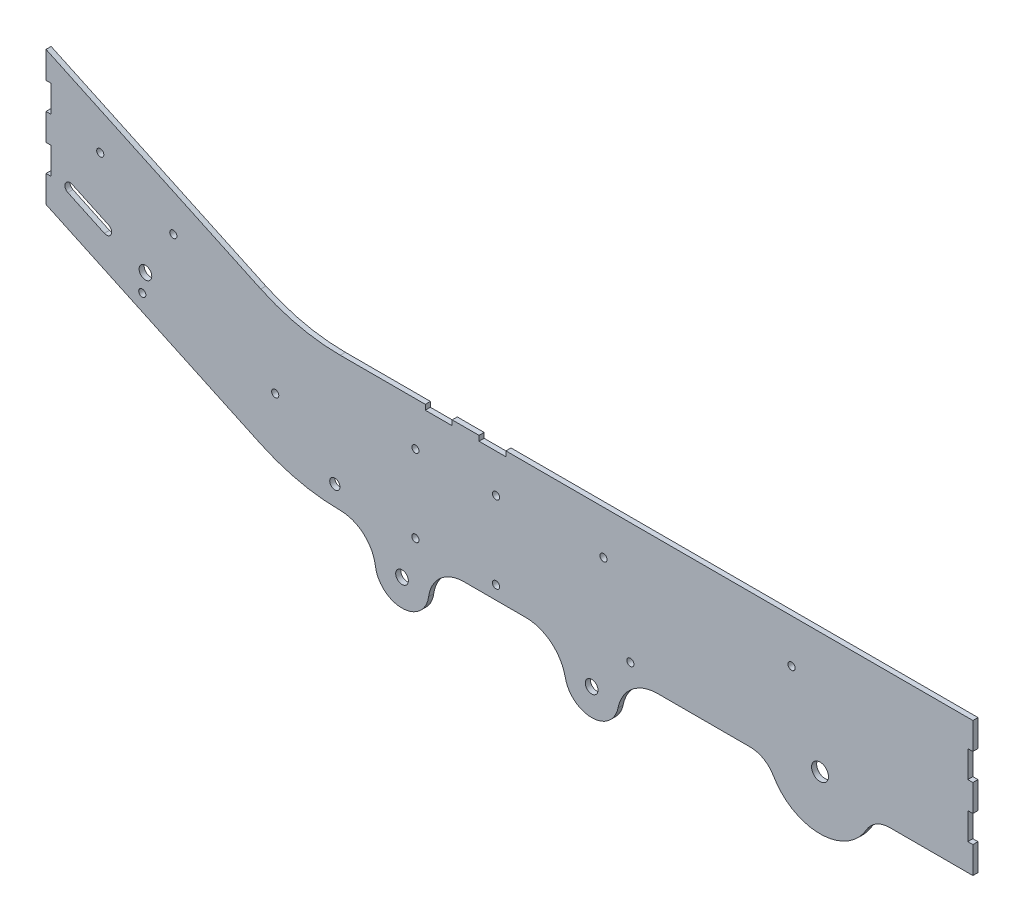
SolidWorks part; units mm, degrees
material "1060 Alloy"
ref_plane "Front Plane" through (0, 0, 0) normal (0, 0, 1) x (1, 0, 0)
ref_plane "Top Plane" through (0, 0, 0) normal (0, 1, 0) x (1, 0, 0)
ref_plane "Right Plane" through (0, 0, 0) normal (1, 0, 0) x (0, 0, -1)
sketch "standoff holes lower" plane through (0, 0, 0) normal (0, 0, 1) x (1, 0, 0)
  circle A7 centre (95.25, 85.725) radius 3.3782
  circle A8 centre (95.25, 12.7) radius 3.3782
  circle A9 centre (171.45, 12.7) radius 3.3782
  circle A10 centre (171.45, 85.725) radius 3.3782
  circle A12 centre (298.45, 12.7) radius 3.3782
  circle A13 centre (450.85, 85.725) radius 3.3782
  circle A16 centre (273.05, 85.725) radius 3.3782
  point P21 (0, 0)
sketch "axle holes lower" plane through (0, 0, 0) normal (0, 0, 1) x (1, 0, 0)
  line L10 (514.35, 98.425) -> (75.4368, 98.425) construction
  line L11 (66.0749, 94.3067) -> (3.3381, 25.8666) construction
  line L12 (0, 17.2849) -> (0, 12.7) construction
  line L13 (12.7, 0) -> (514.35, 0) construction
  line L14 (527.05, 12.7) -> (527.05, 85.725) construction
  circle A1 centre (247.65, 15.24) radius 4.826
  circle A4 centre (19.05, 19.05) radius 4.826
  arc A10 (527.05, 85.725) -> (514.35, 98.425) centre (514.35, 85.725) ccw construction
  arc A11 (75.4368, 98.425) -> (66.0749, 94.3067) centre (75.4368, 85.725) ccw construction
  arc A12 (3.3381, 25.8666) -> (0, 17.2849) centre (12.7, 17.2849) ccw construction
  arc A13 (0, 12.7) -> (12.7, 0) centre (12.7, 12.7) ccw construction
  arc A14 (514.35, 0) -> (527.05, 12.7) centre (514.35, 12.7) ccw construction
  circle A15 centre (476.25, 19.05) radius 4.826
sketch "lower box" plane through (0, 0, 0) normal (0, 0, 1) x (1, 0, 0)
  line L1 (622.3, 0) -> (-254, 0) construction
  line L2 (622.3, 0) -> (622.3, 25.4) construction
  line L3 (622.3, 127) -> (-254, 127) construction
  line L4 (-254, 0) -> (-254, 127) construction
  line L6 (527.05, 12.7) -> (527.05, 85.725) construction
  line L7 (622.3, 101.6) -> (622.3, 127) construction
  line L8 (622.3, 101.6) -> (617.474, 101.6) construction
  line L10 (622.3, 76.2) -> (617.474, 76.2) construction
  line L11 (617.474, 101.6) -> (617.474, 76.2) construction
  line L12 (622.3, 50.8) -> (617.474, 50.8) construction
  line L14 (622.3, 25.4) -> (617.474, 25.4) construction
  line L15 (617.474, 50.8) -> (617.474, 25.4) construction
  line L16 (622.3, 50.8) -> (622.3, 76.2) construction
  dimension "D1" = 127
  dimension "D2" = 876.3
  dimension "D3" = 95.25
  dimension "D4" = 4.826
sketch "alxe holes upper" plane through (0, 0, 0) normal (0, 0, 1) x (1, 0, 0)
  line L0 (-219.7848, 130.4205) -> (-230.5193, 107.4003) construction
  line L1 (-230.5193, 107.4003) -> (8.3155, -3.9702) construction
  line L3 (8.3155, -3.9702) -> (19.05, 19.05) construction
  line L4 (622.3, 0) -> (-254, 0) construction
  circle A0 centre (19.05, 19.05) radius 4.826 construction
  circle A2 centre (-219.7848, 130.4205) radius 4.826
  circle A3 centre (19.05, 19.05) radius 4.826
  dimension "D4" = 25
  dimension "D1" = 25.4
  dimension "D2" = 25.4
  dimension "D3" = 263.525
sketch "standoff holes upper" plane through (0, 0, 0) normal (0, 0, 1) x (1, 0, 0)
  line L0 (-162.9561, 84.3028) -> (-166.1764, 77.3967) construction
  line L1 (-226.6865, 105.613) -> (11.2395, -5.3337) construction
  line L4 (-37.2808, 64.9356) -> (-55.5295, 25.8012) construction
  line L5 (-230.5193, 107.4003) -> (8.3155, -3.9702) construction
  circle A2 centre (-162.9561, 84.3028) radius 3.3782
  circle A3 centre (-37.2808, 64.9356) radius 3.3782
  dimension "D2" = 7.62
  dimension "D1" = 43.18
sketch "upper shadow" plane through (0, 0, 0) normal (0, 0, 1) x (1, 0, 0)
  line L0 (-230.5193, 107.4003) -> (8.3155, -3.9702) construction
  line L4 (33.2535, 40.1076) -> (-204.2179, 150.8423) construction
  line L5 (-230.5193, 107.4003) -> (8.3155, -3.9702) construction
  arc A4 (8.3155, -3.9702) -> (33.2535, 40.1076) centre (19.05, 19.05) ccw construction
  arc A5 (-204.2179, 150.8423) -> (-230.5193, 107.4003) centre (-216.8161, 128.7868) ccw construction
  dimension "D1" = 25.4
  dimension "D2" = 25.4
sketch "upper box" plane through (0, 0, 0) normal (0, 0, 1) x (1, 0, 0)
  line L0 (-15.224, 0) -> (-254, 111.3431) construction
  line L1 (622.3, 0) -> (-254, 0) construction
  line L2 (-254, 111.3431) -> (-254, 136.7431) construction
  line L3 (-254, 238.3431) -> (257.1283, 0) construction
  line L4 (12.7, 0) -> (514.35, 0) construction
  line L5 (-254, 0) -> (-254, 127) construction
  line L6 (-230.5193, 107.4003) -> (8.3155, -3.9702) construction
  line L7 (-254, 212.9431) -> (-254, 238.3431) construction
  line L8 (-254, 212.9431) -> (-249.174, 212.9431) construction
  line L9 (-254, 162.1431) -> (-254, 187.5431) construction
  line L10 (-254, 187.5431) -> (-249.174, 187.5431) construction
  line L11 (-249.174, 212.9431) -> (-249.174, 187.5431) construction
  line L12 (-254, 162.1431) -> (-249.174, 162.1431) construction
  line L14 (-254, 136.7431) -> (-249.174, 136.7431) construction
  line L15 (-249.174, 162.1431) -> (-249.174, 136.7431) construction
  dimension "D1" = 127
  dimension "D2" = 6.35
  dimension "D3" = 4.826
sketch "outer face" plane through (0, 0, 0) normal (0, 0, 1) x (1, 0, 0)
  line L0 (622.3, 0) -> (-254, 0) construction
  line L1 (622.3, 0) -> (622.3, 25.4) construction
  line L2 (622.3, 25.4) -> (617.474, 25.4) construction
  line L3 (617.474, 50.8) -> (617.474, 25.4) construction
  line L4 (622.3, 50.8) -> (617.474, 50.8) construction
  line L5 (622.3, 50.8) -> (622.3, 76.2) construction
  line L6 (622.3, 76.2) -> (617.474, 76.2) construction
  line L7 (617.474, 101.6) -> (617.474, 76.2) construction
  line L8 (622.3, 101.6) -> (622.3, 127) construction
  line L9 (622.3, 101.6) -> (617.474, 101.6) construction
  line L10 (622.3, 127) -> (-254, 127) construction
  line L11 (-254, 238.3431) -> (257.1283, 0) construction
  line L12 (-254, 212.9431) -> (-254, 238.3431) construction
  line L13 (-254, 212.9431) -> (-249.174, 212.9431) construction
  line L14 (-249.174, 212.9431) -> (-249.174, 187.5431) construction
  line L15 (-249.174, 162.1431) -> (-249.174, 136.7431) construction
  line L16 (-254, 136.7431) -> (-249.174, 136.7431) construction
  line L17 (-254, 111.3431) -> (-254, 136.7431) construction
  line L18 (-15.224, 0) -> (-254, 111.3431) construction
  line L19 (-254, 162.1431) -> (-249.174, 162.1431) construction
  line L20 (-254, 162.1431) -> (-254, 187.5431) construction
  line L21 (-254, 187.5431) -> (-249.174, 187.5431) construction
  line L22 (622.3, 0) -> (24.1933, 0)
  line L23 (622.3, 0) -> (622.3, 25.4)
  line L24 (622.3, 25.4) -> (617.474, 25.4)
  line L25 (617.474, 50.8) -> (617.474, 25.4)
  line L26 (622.3, 50.8) -> (617.474, 50.8)
  line L27 (622.3, 50.8) -> (622.3, 76.2)
  line L28 (622.3, 76.2) -> (617.474, 76.2)
  line L29 (617.474, 101.6) -> (617.474, 76.2)
  line L30 (622.3, 101.6) -> (622.3, 127)
  line L31 (622.3, 101.6) -> (617.474, 101.6)
  line L32 (622.3, 127) -> (24.1933, 127)
  line L33 (-254, 238.3431) -> (-50.9483, 143.6585)
  line L34 (-254, 212.9431) -> (-254, 238.3431)
  line L35 (-254, 212.9431) -> (-249.174, 212.9431)
  line L36 (-249.174, 212.9431) -> (-249.174, 187.5431)
  line L37 (-249.174, 162.1431) -> (-249.174, 136.7431)
  line L38 (-254, 136.7431) -> (-249.174, 136.7431)
  line L39 (-254, 111.3431) -> (-254, 136.7431)
  line L40 (-50.9483, 16.6585) -> (-254, 111.3431)
  line L41 (-254, 162.1431) -> (-249.174, 162.1431)
  line L42 (-254, 162.1431) -> (-254, 187.5431)
  line L43 (-254, 187.5431) -> (-249.174, 187.5431)
  arc A0 (-50.9483, 16.6585) -> (24.1933, 0) centre (24.1933, 177.8) ccw
  arc A1 (24.1933, 127) -> (-50.9483, 143.6585) centre (24.1933, 304.8) cw
  dimension "D1" = 177.8
extrude "Boss-Extrude1" add sketch "outer face" along normal blind 4.826
sketch "Sketch5" plane through (0, 0, 4.826) normal (0, 0, 1) x (1, 0, 0)
  line L0 (-254, 238.3431) -> (257.1283, 0) construction
  line L1 (-162.9561, 84.3028) -> (-120.2162, 175.9587) construction
  line L3 (-202.695, 179.3869) -> (-133.6344, 147.1834) construction
  circle A0 centre (-162.9561, 84.3028) radius 3.3782 construction
  circle A1 centre (-37.2808, 64.9356) radius 3.3782 construction
  circle A2 centre (95.25, 85.725) radius 3.3782 construction
  circle A3 centre (95.25, 12.7) radius 3.3782 construction
  circle A4 centre (171.45, 12.7) radius 3.3782 construction
  circle A5 centre (171.45, 85.725) radius 3.3782 construction
  circle A6 centre (273.05, 85.725) radius 3.3782 construction
  circle A7 centre (298.45, 12.7) radius 3.3782 construction
  circle A8 centre (450.85, 85.725) radius 3.3782 construction
  circle A9 centre (-162.9561, 84.3028) radius 3.3782
  circle A10 centre (-37.2808, 64.9356) radius 3.3782
  circle A11 centre (95.25, 85.725) radius 3.3782
  circle A12 centre (95.25, 12.7) radius 3.3782
  circle A13 centre (171.45, 12.7) radius 3.3782
  circle A14 centre (171.45, 85.725) radius 3.3782
  circle A15 centre (273.05, 85.725) radius 3.3782
  circle A16 centre (298.45, 12.7) radius 3.3782
  circle A17 centre (450.85, 85.725) radius 3.3782
  circle A18 centre (-133.6344, 147.1834) radius 3.3782
  circle A19 centre (-202.695, 179.3869) radius 3.3782
  dimension "D1" = 31.75
  dimension "D2" = 76.2
extrude "standoff hole" cut sketch "Sketch5" against normal through all
sketch "Sketch6" plane through (0, 0, 4.826) normal (0, 0, 1) x (1, 0, 0)
  circle A0 centre (-219.7848, 130.4205) radius 4.826 construction
  circle A1 centre (19.05, 19.05) radius 4.826 construction
  circle A2 centre (247.65, 15.24) radius 4.826 construction
  circle A4 centre (-219.7848, 130.4205) radius 4.826
  circle A5 centre (19.05, 19.05) radius 4.826
  circle A6 centre (247.65, 15.24) radius 4.826 construction
extrude "axle holes" cut sketch "Sketch6" against normal through all
sketch "Sketch7" plane through (0, 0, 4.826) normal (0, 0, 1) x (1, 0, 0)
  line L0 (-231.2949, 135.7877) -> (-196.7645, 119.686) construction
  line L1 (-229.2553, 140.1616) -> (-194.725, 124.0598)
  line L2 (-233.3344, 131.4139) -> (-198.8041, 115.3121)
  line L3 (-230.5193, 107.4003) -> (8.3155, -3.9702) construction
  circle A0 centre (-219.7848, 130.4205) radius 4.826 construction
  circle A1 centre (-219.7848, 130.4205) radius 4.826
  arc A2 (-229.2553, 140.1616) -> (-233.3344, 131.4139) centre (-231.2949, 135.7877) ccw
  arc A3 (-198.8041, 115.3121) -> (-194.725, 124.0598) centre (-196.7645, 119.686) ccw
  point P5 (-214.0297, 127.7369)
  circle M6 centre (-219.7848, 130.4205) radius 4.826
  dimension "D1" = 38.1
  dimension "D2" = 12.7
extrude "front slot" cut sketch "Sketch7" against normal through all contours L1 A2 L2 A1 M6 | L2 A3 L1 region at (-228.975, 134.706, 4.826) region at (-204.8394, 123.4514, 4.826)
sketch "Sketch8" plane through (0, 0, 4.826) normal (0, 0, 1) x (1, 0, 0)
  line L0 (129.9864, 127) -> (129.9864, 122.174) construction
  line L1 (104.5864, 122.174) -> (129.9864, 122.174)
  line L2 (104.5864, 122.174) -> (104.5864, 127)
  line L3 (104.5864, 127) -> (129.9864, 127)
  line L4 (129.9864, 122.174) -> (129.9864, 127)
  line L5 (622.3, 127) -> (24.1933, 127) construction
  line L6 (129.9864, 122.174) -> (155.3864, 122.174) construction
  line L7 (155.3864, 122.174) -> (180.7864, 122.174)
  line L8 (155.3864, 122.174) -> (155.3864, 127)
  line L9 (155.3864, 127) -> (180.7864, 127)
  line L10 (180.7864, 122.174) -> (180.7864, 127)
  line L11 (79.1864, 122.174) -> (206.1864, 122.174)
  line L12 (79.1864, 122.174) -> (79.1864, 127)
  line L13 (79.1864, 127) -> (206.1864, 127)
  line L14 (206.1864, 122.174) -> (206.1864, 127)
  point P18 (142.6864, 122.174)
  point P19 (142.6864, 122.174)
  line M29 (622.3, 127) -> (24.1933, 127)
  dimension "D1" = 127
extrude "top slots" cut sketch "Sketch8" against normal through all contours L1 L4 L2 M29 | L7 L10 L8 M29 region at (117.2864, 124.587, 4.826) region at (168.0864, 124.587, 4.826)
sketch "Sketch9" plane through (0, 0, 4.826) normal (0, 0, 1) x (1, 0, 0)
  line L0 (365.4629, -63.5) -> (553.974, -63.5) construction
  line L1 (24.1933, 0) -> (622.3, 0) construction
  line L3 (553.974, -63.5) -> (553.974, 63.787) construction
  line L4 (617.474, 25.4) -> (617.474, 50.8) construction
  line L5 (24.1933, 0) -> (622.3, 0)
  circle A0 centre (477.774, 12.7) radius 76.2 construction
  circle A1 centre (477.774, 12.7) radius 8
  arc A2 (433.7799, -12.7) -> (521.7681, -12.7) centre (477.774, 12.7) ccw
  arc A3 (543.7651, 0) -> (521.7681, -12.7) centre (543.7651, -25.4) ccw
  arc A4 (433.7799, -12.7) -> (411.7829, 0) centre (411.7829, -25.4) ccw
  dimension "D1" = 152.4
  dimension "D4" = 16
  dimension "D5" = 50.8
  dimension "D6" = 25.4
  dimension "D7" = 25.4
  dimension "D2" = 63.5
  dimension "D3" = 63.5
extrude "back axle extension" add sketch "Sketch9" against normal up to surface (4.826 mm away) contours A4 A2 A3 L5 region at (477.774, -15.4671, 4.826) up to face at (-214.0297, 127.7369, 0)
sketch "Sketch11" plane through (0, 0, 4.826) normal (0, 0, 1) x (1, 0, 0)
  line L0 (24.1933, 0) -> (411.7829, 0) construction
  line L1 (24.1933, 0) -> (411.7829, 0)
  line L2 (561.7812, -62.775) -> (321.8375, -62.775) construction
  line L3 (199.6366, 0) -> (324.1114, 0)
  arc A0 (471.7538, 87.9345) -> (489.1691, 87.3098) centre (477.774, 12.7) ccw construction
  arc A1 (471.7538, 87.9345) -> (489.1691, 87.3098) centre (477.774, 12.7) ccw
  circle A2 centre (261.874, -25.5) radius 37.275 construction
  arc A5 (258.0857, 11.582) -> (275.1308, 9.338) centre (261.874, -25.5) ccw construction
  arc A6 (258.0857, 11.582) -> (275.1308, 9.338) centre (261.874, -25.5) ccw construction
  arc A7 (236.9791, -30.54) -> (286.7689, -30.54) centre (261.874, -25.5) ccw
  arc A8 (324.1114, 0) -> (286.7689, -30.54) centre (324.1114, -38.1) ccw
  arc A9 (236.9791, -30.54) -> (199.6366, 0) centre (199.6366, -38.1) ccw
  dimension "D1" = 215.9
  dimension "D2" = 25.4
  dimension "D3" = 38.1
extrude "lower small axle extension" add sketch "Sketch11" against normal up to surface (4.826 mm away) contours A9 A7 A8 L1 region at (261.874, -20.0987, 4.826) up to face at (-214.0297, 127.7369, 0)
sketch "Sketch13" plane through (0, 0, 4.826) normal (0, 0, 1) x (1, 0, 0)
  line L0 (247.3066, -62.775) -> (540.2367, -62.775) construction
  line L1 (-361.4832, 140.4439) -> (-108.3874, 22.4235) construction
  line L2 (-229.2553, 140.1616) -> (-194.725, 124.0598) construction
  line L3 (24.1933, 0) -> (199.6366, 0) construction
  line L4 (24.1933, 0) -> (199.6366, 0)
  arc A0 (471.7538, 87.9345) -> (489.1691, 87.3098) centre (477.774, 12.7) ccw construction
  arc A1 (258.0857, 11.582) -> (275.1308, 9.338) centre (261.874, -25.5) ccw construction
  arc A2 (471.7538, 87.9345) -> (489.1691, 87.3098) centre (477.774, 12.7) ccw construction
  arc A3 (258.0857, 11.582) -> (275.1308, 9.338) centre (261.874, -25.5) ccw construction
  circle A5 centre (82.5849, -25.5) radius 37.275 construction
  arc A6 (-198.8041, 115.3121) -> (-194.725, 124.0598) centre (-196.7645, 119.686) ccw construction
  arc A7 (-198.8041, 115.3121) -> (-194.725, 124.0598) centre (-196.7645, 119.686) ccw construction
  circle A8 centre (-196.7645, 119.686) radius 50.8 construction
  arc A9 (57.4225, -28.9659) -> (107.7473, -28.9659) centre (82.5849, -25.5) ccw
  arc A12 (236.9791, -30.54) -> (286.7689, -30.54) centre (261.874, -25.5) ccw construction
  arc A13 (140.9765, 0) -> (107.7473, -28.9659) centre (140.9765, -33.543) ccw
  arc A14 (57.4225, -28.9659) -> (24.1933, 0) centre (24.1933, -33.543) ccw
  dimension "D1" = 101.6
extrude "front small axle extension" add sketch "Sketch13" against normal up to surface (4.826 mm away) contours A14 A9 A13 L4 region at (82.5849, -20.4486, 4.826) up to face at (-214.0297, 127.7369, 0)
sketch "Sketch14" plane through (0, 0, 4.826) normal (0, 0, 1) x (1, 0, 0)
  line L0 (-254, 111.3431) -> (-50.9483, 16.6585) construction
  line L1 (-254, 111.3431) -> (-50.9483, 16.6585)
  line L2 (-267.5177, 96.6271) -> (94.0166, -71.9591) construction
  line L3 (-227.5206, 77.9761) -> (-175.6892, 189.1288) construction
  arc A0 (78.7966, 11.582) -> (95.8417, 9.338) centre (82.5849, -25.5) ccw construction
  arc A1 (78.7966, 11.582) -> (95.8417, 9.338) centre (82.5849, -25.5) ccw
  circle A2 centre (-160.0111, 102.5476) radius 50.8 construction
  dimension "D1" = 101.6
  dimension "D2" = 38.1
sketch "Sketch10" plane through (0, 0, 4.826) normal (0, 0, 1) x (1, 0, 0)
  circle A0 centre (477.774, 12.7) radius 8
  circle A1 centre (261.874, -25.5) radius 6
  circle A2 centre (82.5849, -25.5) radius 6
  circle A3 centre (-160.0111, 102.5476) radius 6
  dimension "D1" = 16
  dimension "D2" = 12
  dimension "D3" = 12
extrude "new axle holes" cut sketch "Sketch10" against normal through all
equation "\"w\"= .19"
equation "\"D4@lower box\" = \"w\""
equation "\"D3@upper box\"=\"w\""
equation "\"D1@Boss-Extrude1\"=\"w\""
